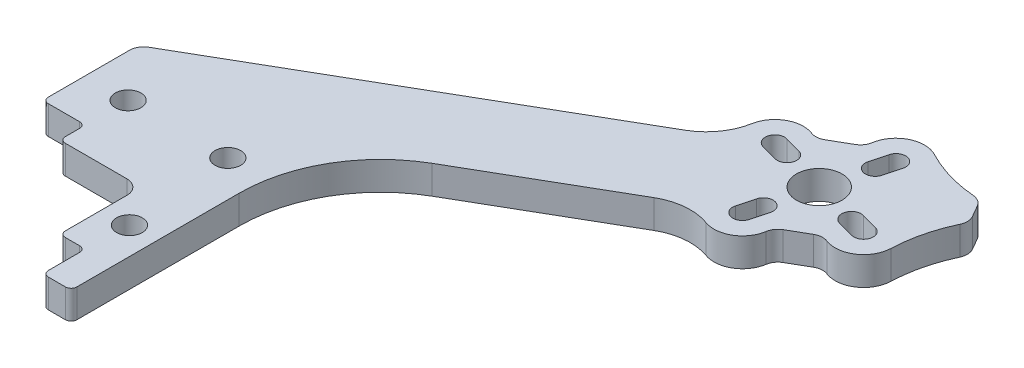
SolidWorks part; units mm, degrees
material "Thornel Mat VMA"
ref_plane "Front Plane" through (0, 0, 0) normal (0, 0, 1) x (1, 0, 0)
ref_plane "Top Plane" through (0, 0, 0) normal (0, 1, 0) x (1, 0, 0)
ref_plane "Right Plane" through (0, 0, 0) normal (1, 0, 0) x (0, 0, -1)
sketch "Sketch1" plane through (0, 0, 0) normal (0, 1, 0) x (1, 0, 0)
  line L0 (0, 0) -> (81.3173, 81.3173) construction
  line L1 (-31.35, -29.5) -> (31.35, -29.5) construction
  line L2 (-31.35, -29.5) -> (-31.35, 29.5) construction
  line L3 (-31.35, 29.5) -> (31.35, 29.5) construction
  line L4 (31.35, -29.5) -> (31.35, 29.5) construction
  line L5 (0, 29.5) -> (0, -29.5) construction
  line L6 (-31.35, 0) -> (31.35, 0) construction
  line L7 (31.35, 0) -> (26.35, 0)
  line L8 (26.35, 0) -> (26.35, 7.5)
  line L9 (26.35, 7.5) -> (21.825, 7.5)
  line L10 (21.825, 7.5) -> (21.825, 21.825)
  line L11 (7.5, 21.825) -> (21.825, 21.825)
  line L12 (7.5, 26.35) -> (7.5, 21.825)
  line L13 (0, 26.35) -> (7.5, 26.35)
  line L14 (0, 26.35) -> (0, 43.029)
  line L15 (0, 34.3687) -> (81.3173, 81.3173) construction
  line L16 (31.35, 0) -> (31.35, 29.5)
  line L17 (0, 43.029) -> (60.9385, 78.2119)
  line L18 (68.4385, 65.2215) -> (43.7414, 50.9626)
  line L19 (83.3878, 89.0447) -> (79.2467, 73.5899) construction
  line L20 (83.3878, 89.0447) -> (84.1643, 91.9425) construction
  line L21 (81.7458, 89.4847) -> (82.5222, 92.3825)
  line L22 (85.0299, 88.6047) -> (85.8064, 91.5025)
  line L23 (89.0447, 79.2467) -> (91.9425, 78.4703) construction
  line L24 (89.4847, 80.8888) -> (92.3825, 80.1123)
  line L25 (88.6047, 77.6047) -> (91.5025, 76.8282)
  line L26 (79.2467, 73.5899) -> (78.4703, 70.6921) construction
  line L27 (80.8888, 73.1499) -> (80.1123, 70.2521)
  line L28 (77.6047, 74.0299) -> (76.8282, 71.1321)
  line L29 (73.5899, 83.3878) -> (70.6921, 84.1643) construction
  line L30 (73.1499, 81.7458) -> (70.2521, 82.5222)
  line L31 (74.0299, 85.0299) -> (71.1321, 85.8064)
  line L32 (74.6275, 89.002) -> (78.007, 90.9531)
  line L33 (84.6275, 71.6815) -> (88.007, 73.6326)
  line L34 (97.3878, 93.4823) -> (99.8878, 89.1522)
  line L35 (98.6378, 91.3173) -> (81.3173, 81.3173) construction
  arc A0 (31.35, 29.5) -> (43.7414, 50.9626) centre (56.1329, 29.5) cw
  circle A1 centre (81.3173, 81.3173) radius 4
  arc A2 (81.7458, 89.4847) -> (85.0299, 88.6047) centre (83.3878, 89.0447) ccw
  arc A3 (85.8064, 91.5025) -> (82.5222, 92.3825) centre (84.1643, 91.9425) ccw
  arc A4 (89.4847, 80.8888) -> (88.6047, 77.6047) centre (89.0447, 79.2467) ccw
  arc A5 (91.5025, 76.8282) -> (92.3825, 80.1123) centre (91.9425, 78.4703) ccw
  arc A6 (80.8888, 73.1499) -> (77.6047, 74.0299) centre (79.2467, 73.5899) ccw
  arc A7 (76.8282, 71.1321) -> (80.1123, 70.2521) centre (78.4703, 70.6921) ccw
  arc A8 (73.1499, 81.7458) -> (74.0299, 85.0299) centre (73.5899, 83.3878) ccw
  arc A9 (71.1321, 85.8064) -> (70.2521, 82.5222) centre (70.6921, 84.1643) ccw
  arc A10 (65.7742, 85.0669) -> (72.4824, 88.8328) centre (70.6921, 84.1643) cw
  arc A11 (79.2261, 92.7263) -> (86.4994, 96.3637) centre (84.1643, 91.9425) cw
  arc A12 (86.4994, 96.3637) -> (97.3878, 93.4823) centre (98.1747, 118.47) ccw
  arc A13 (72.4824, 88.8328) -> (74.6275, 89.002) centre (73.3775, 91.167) ccw
  arc A14 (65.7742, 85.0669) -> (60.9385, 78.2119) centre (55.9385, 86.8721) cw
  arc A15 (78.007, 90.9531) -> (79.2261, 92.7263) centre (76.757, 93.1182) ccw
  arc A16 (96.9389, 78.2819) -> (99.8878, 89.1522) centre (121.9212, 77.3399) cw
  arc A17 (90.1522, 73.8018) -> (96.9389, 78.2819) centre (91.9425, 78.4703) ccw
  arc A18 (88.007, 73.6326) -> (90.1522, 73.8018) centre (89.257, 71.4675) cw
  arc A19 (83.4085, 69.9083) -> (84.6275, 71.6815) centre (85.8775, 69.5164) cw
  arc A20 (76.793, 65.9818) -> (83.4085, 69.9083) centre (78.4703, 70.6921) ccw
  arc A21 (76.793, 65.9818) -> (68.4385, 65.2215) centre (73.4385, 56.5612) ccw
  point P0 (0, 0)
  point P21 (83.7761, 90.4936)
  point P29 (81.3173, 81.3173)
  point P33 (90.4936, 78.8585)
  point P40 (78.8585, 72.141)
  point P47 (72.141, 83.7761)
  point P54 (81.3173, 81.3173)
  dimension "D11" = 8
  dimension "D13" = 1.7
  dimension "D17" = 5
  dimension "D18" = 25
  dimension "D22" = 2.5
  dimension "D23" = 10
  dimension "D1" = 62.7
  dimension "D2" = 59
  dimension "D3" = 45
  dimension "D4" = 115
  dimension "D5" = 5
  dimension "D6" = 9.525
  dimension "D7" = 7.5
  dimension "D8" = 30
  dimension "D9" = 7.5
  dimension "D10" = 43.029
  dimension "D12" = 45
  dimension "D14" = 3
  dimension "D15" = 8
  dimension "D19" = 20
  dimension "D20" = 2.5
  dimension "D21" = 10
  dimension "D16" = 4
extrude "Boss-Extrude1" add sketch "Sketch1" along normal mid plane 5 contours A21 A20 A19 L33 A18 A17 A16 L34 A12 A11 A15 L32 A13 A10 A14 L17 L14 L13 L12 L11 L10 L9 L8 L7 L16 A0 L18 A9 L31 A8 L30 A7 L28 A6 L27 A5 L25 A4 L24 A3 L22 A2 L21 A1 region at (43.3878, 0, -53.7467)
fillet "Fillet1" radius 2.5 4 edges at (99.8878, 0, -89.1522) (97.3878, 0, -93.4823) (0, 0, -43.029) (21.825, 0, -21.825)
fillet "Fillet2" radius 1 7 edges at (26.35, 0, 0) (26.35, 0, -7.5) (21.825, 0, -7.5) (0, 0, -26.35) (7.5, 0, -21.825) (7.5, 0, -26.35) (31.35, 0, 0)
hole_wizard "M4 Clearance Hole1" positions "Sketch2" profile "Sketch3" hole size "M4" standard "ANSI Metric" end condition through all
sketch "Sketch2" plane through (0, 2.5, 0) normal (0, 1, 0) x (1, 0, 0)
  line L0 (31.35, 1) -> (31.35, 29.5) construction
  line L1 (30.35, 0) -> (27.35, 0) construction
  line L2 (1, 26.35) -> (6.5, 26.35) construction
  line L3 (0, 27.35) -> (0, 41.5856) construction
  line L4 (0, 27.35) -> (0, 41.5856) construction
  point P0 (26.5875, 15)
  point P2 (7.5, 33.85)
  point P4 (25, 33.85)
  dimension "D1" = 4.7625
  dimension "D2" = 15
  dimension "D3" = 7.5
  dimension "D4" = 7.5
  dimension "D5" = 25
sketch "Sketch3" plane through (26.5875, 2.5, -15) normal (1, 0, 0) x (0, 0, 1)
  line L0 (0, 0) -> (0, 5)
  line L1 (0, 5) -> (2.25, 5)
  line L2 (2.25, 5) -> (2.25, 0)
  line L5 (2.25, 0) -> (0, 0)
  line L11 (0, -6.35) -> (0, 107.95) construction
  dimension "Thru Hole Dia." = 4.5
  dimension "Thru Hole Depth" = 5
